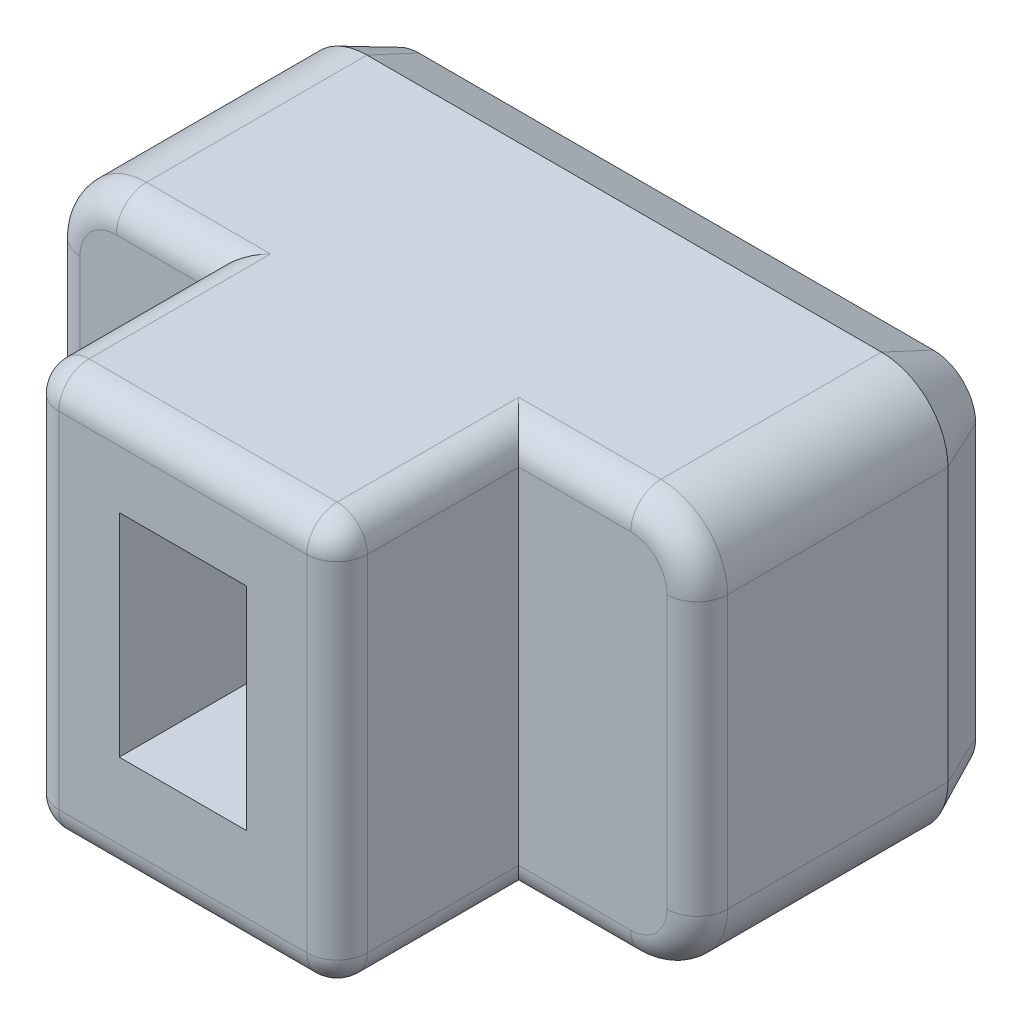
SolidWorks part; units mm, degrees
ref_plane "Plan de face" through (0, 0, 0) normal (0, 0, 1) x (1, 0, 0)
ref_plane "Plan de dessus" through (0, 0, 0) normal (0, 1, 0) x (1, 0, 0)
ref_plane "Plan de droite" through (0, 0, 0) normal (1, 0, 0) x (0, 0, -1)
sketch "Esquisse2" plane through (0, 0, 0) normal (0, 0, 1) x (1, 0, 0)
  line L1 (1.1, 0) -> (9.6, 0)
  line L2 (0, 1.1) -> (0, 5.6)
  line L3 (1.1, 6.7) -> (9.6, 6.7)
  line L4 (10.7, 1.1) -> (10.7, 5.6)
  arc A0 (9.6, 6.7) -> (10.7, 5.6) centre (9.6, 5.6) cw
  arc A1 (9.6, 0) -> (10.7, 1.1) centre (9.6, 1.1) ccw
  arc A2 (1.1, 0) -> (0, 1.1) centre (1.1, 1.1) cw
  arc A3 (0, 5.6) -> (1.1, 6.7) centre (1.1, 5.6) cw
  point P7 (10.7, 6.7)
  point P12 (0, 0)
  point P15 (0, 6.7)
  dimension "D3" = 1.1
  dimension "D1" = 10.7
  dimension "D2" = 6.7
extrude "Boss.-Extru.1" add sketch "Esquisse2" along normal blind 8
sketch "Esquisse3" plane through (0, 0, 8) normal (0, 0, 1) x (1, 0, 0)
  line L0 (0, 5.6) -> (0, 1.1) construction
  line L1 (4.15, 5.25) -> (6.25, 5.25)
  line L2 (4.15, 5.25) -> (4.15, 1.75)
  line L3 (4.15, 1.75) -> (6.25, 1.75)
  line L4 (6.25, 5.25) -> (6.25, 1.75)
  line L5 (10.7, 1.1) -> (10.7, 5.6) construction
  line L6 (9.6, 6.7) -> (1.1, 6.7) construction
  line L7 (1.1, 0) -> (9.6, 0) construction
  dimension "D1" = 2.1
  dimension "D2" = 3.5
  dimension "D3" = 4.15
  dimension "D4" = 4.45
  dimension "D5" = 1.45
  dimension "D6" = 1.75
extrude "Enlèv. mat.-Extru.1" cut sketch "Esquisse3" against normal blind 3
sketch "Esquisse4" plane through (0, 0, 8) normal (0, 0, 1) x (1, 0, 0)
  line L0 (2.65, 6.7) -> (2.65, 0)
  line L1 (9.6, 6.7) -> (1.1, 6.7) construction
  line L2 (1.1, 0) -> (9.6, 0) construction
  line L3 (2.65, 0) -> (7.75, 0)
  line L4 (7.75, 0) -> (7.75, 6.7)
  line L5 (7.75, 6.7) -> (2.65, 6.7)
  line L6 (4.15, 5.25) -> (4.15, 1.75) construction
  line L7 (6.25, 1.75) -> (6.25, 5.25) construction
  dimension "D1" = 1.5
  dimension "D2" = 1.5
extrude "Enlèv. mat.-Extru.2" cut sketch "Esquisse4" against normal blind 3 flip side to cut
fillet "Congé1" radius 0.5 18 edges at (8.675, 0, 5) (10.3778, 0.3222, 5) (10.7, 3.35, 5) (10.3778, 6.3778, 5) (1.875, 6.7, 5) (0.3222, 6.3778, 5) (1.875, 0, 5) (0.3222, 0.3222, 5) (7.75, 6.7, 6.5) (2.65, 6.7, 6.5) (7.75, 0, 6.5) (2.65, 0, 6.5) (2.65, 3.35, 8) (5.2, 6.7, 8) (7.75, 3.35, 8) (5.2, 0, 8) (8.675, 6.7, 5) (0, 3.35, 5)
chamfer "Chanfrein1" distance 0.4 angle 65 8 edges at (5.35, 0, 0) (10.3778, 0.3222, 0) (0.3222, 0.3222, 0) (10.7, 3.35, 0) (0, 3.35, 0) (10.3778, 6.3778, 0) (0.3222, 6.3778, 0) (5.35, 6.7, 0) first distance on face at (5.35, 3.35, 0)
sketch "Esquisse5" plane through (0, 0, 0) normal (0, 0, 1) x (1, 0, 0)
  line L0 (-0.9378, 5.093) -> (11.6517, 5.093) construction
  text T0 "MSG" font "Corbel" height 3.5
extrude "Enlèv. mat.-Extru.3" cut sketch "Esquisse5" along normal blind 0.2
extrude "Boss.-Extru.2" add sketch "Esquisse5<4>" against normal blind 0.2
sketch "Esquisse5<4>" plane through (0, 0, 0) normal (0, 0, 1) x (1, 0, 0) same geometry as "Esquisse5"
